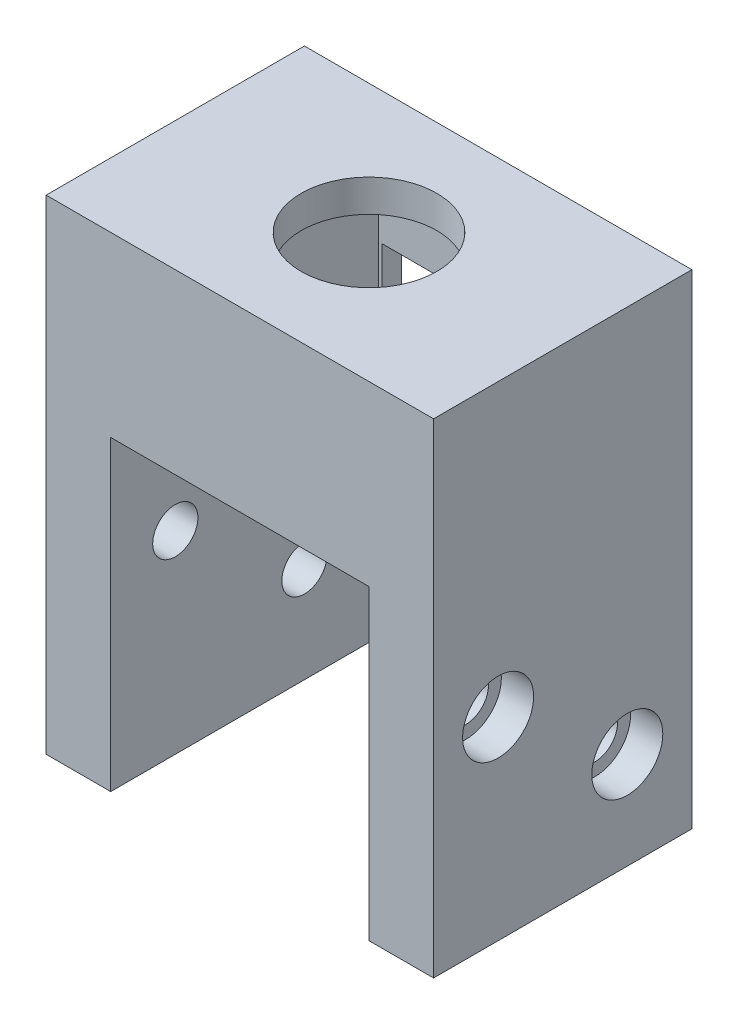
SolidWorks part; units mm, degrees
ref_plane "前视基准面" through (0, 0, 0) normal (0, 0, 1) x (1, 0, 0)
ref_plane "上视基准面" through (0, 0, 0) normal (0, 1, 0) x (1, 0, 0)
ref_plane "右视基准面" through (0, 0, 0) normal (1, 0, 0) x (0, 0, -1)
other "Configuration Table"
sketch "草图1" plane through (0, 0, 0) normal (0, 1, 0) x (1, 0, 0)
  line L0 (-4, 0) -> (4, 0) construction
  line L1 (-4, -4) -> (4, -4)
  line L2 (-4, -4) -> (-4, 4)
  line L3 (-4, 4) -> (4, 4)
  line L4 (4, -4) -> (4, 4)
  line L10 (-4, 4) -> (-6, 4)
  line L11 (-4, 4) -> (-4, -4)
  line L12 (-4, -4) -> (-6, -4)
  line L13 (-6, 4) -> (-6, -4)
  line L14 (4, 4) -> (6, 4)
  line L15 (4, 4) -> (4, -4)
  line L16 (4, -4) -> (6, -4)
  line L17 (6, 4) -> (6, -4)
  circle A0 centre (0, 0) radius 2.1
  dimension "D3" = 4.2
  dimension "D5" = 2
  dimension "D1" = 8
  dimension "D2" = 4
  dimension "D4" = 8
extrude "凸台-拉伸1" add sketch "草图1" along normal blind 1 contours L2 L3 L4 L1 | A0
extrude "凸台-拉伸2" add sketch "草图1<6>" against normal blind 15 from surface separate body contours L10 L13 L12 L2 L11 | L17 L14 L15 L4 L16 region at (-5, 0, 0) region at (5, 0, 0) starting at face at (0, 1, 0)
sketch "草图1<6>" plane through (0, 0, 0) normal (0, 1, 0) x (1, 0, 0) same geometry as "草图1"
sketch "草图2" plane through (0, 0, 0) normal (0, -1, 0) x (1, 0, 0)
  line L0 (4, -4) -> (4, 4) construction
  line L1 (4, 3.4) -> (-4, 3.4)
  line L2 (4, 3.4) -> (4, 4)
  line L3 (4, 4) -> (-4, 4)
  line L4 (-4, 3.4) -> (-4, 4)
  line L5 (-4, 4) -> (4, 4) construction
  line L6 (-4, -4) -> (-4, 4) construction
  line L7 (4, -3.4) -> (-4, -3.4)
  line L8 (4, -3.4) -> (4, -4)
  line L9 (4, -4) -> (-4, -4)
  line L10 (-4, -3.4) -> (-4, -4)
  line L12 (-4, 4) -> (-3.1, 4)
  line L13 (-4, 4) -> (-4, -4)
  line L14 (-4, -4) -> (-3.1, -4)
  line L15 (-3.1, 4) -> (-3.1, -4)
  line L16 (4, 4) -> (3.1, 4)
  line L17 (4, 4) -> (4, -4)
  line L18 (4, -4) -> (3.1, -4)
  line L19 (3.1, 4) -> (3.1, -4)
  line M14 (4, 4) -> (-4, 4)
  line M15 (-4, 4) -> (-4, -4)
  line M16 (-4, -4) -> (4, -4)
  line M17 (4, -4) -> (4, 4)
  dimension "D1" = 0.6
  dimension "D2" = 0.9
extrude "凸台-拉伸3" add sketch "草图2" along normal blind 4.5 contours L15 L3 L1 M15 | L19 L3 L15 L1 | L19 L1 M14 M17 | L1 L19 L7 M17 | L7 L19 M16 M17 | L19 L7 L15 L9 | L15 L7 M15 M16 | L15 L1 L7 M15 region at (3.55, 0, 0) region at (3.55, 0, 3.7) region at (0, 0, 3.7) region at (3.55, 0, -3.7) region at (-3.55, 0, 0) region at (-3.55, 0, 3.7) region at (0, 0, -3.7) region at (-3.55, 0, -3.7)
sketch "草图3" plane through (0, 0, -4) normal (0, 0, -1) x (-1, 0, 0)
  line L0 (4, -4.5) -> (-4, -4.5) construction
  line L1 (-3, -4.5) -> (-1.4, -4.5)
  line L2 (-3, -4.5) -> (-3, -2.5)
  line L3 (-3, -2.5) -> (-1.4, -2.5)
  line L4 (-1.4, -4.5) -> (-1.4, -2.5)
  line L5 (-4, -14) -> (-4, -4.5) construction
  line L6 (1.4, -4.5) -> (3, -4.5)
  line L7 (1.4, -4.5) -> (1.4, -2.5)
  line L8 (1.4, -2.5) -> (3, -2.5)
  line L9 (3, -4.5) -> (3, -2.5)
  line L10 (4, -14) -> (4, -4.5) construction
  line M13 (-4, -4.5) -> (4, -4.5)
  dimension "D1" = 2
  dimension "D2" = 1
  dimension "D3" = 1
  dimension "D4" = 1.6
extrude "切除-拉伸1" cut sketch "草图3" against normal up to next contours L4 L3 L2 M13 | L9 L8 L7 M13 region at (2.2, -3.5, -4) region at (-2.2, -3.5, -4)
sketch "草图4" plane through (6, 0, 0) normal (1, 0, 0) x (0, 0, -1)
  line L0 (-4, -14) -> (4, -14) construction
  line L1 (-4, -14) -> (-4, 1) construction
  line L2 (4, -14) -> (4, 1) construction
  circle A0 centre (-2, -8) radius 1.1
  circle A1 centre (-2, -8) radius 0.7
  circle A2 centre (2, -11) radius 1.1
  circle A3 centre (2, -11) radius 0.7
  dimension "D1" = 1.4
  dimension "D2" = 2.2
  dimension "D3" = 6
  dimension "D4" = 3
  dimension "D5" = 2
  dimension "D6" = 2
extrude "切除-拉伸2" cut sketch "草图4" against normal through all contours A1 | A3
extrude "切除-拉伸3" cut sketch "草图4<3>" against normal blind 1 contours A0 | A2
sketch "草图4<3>" plane through (6, 0, 0) normal (1, 0, 0) x (0, 0, -1) same geometry as "草图4"
extrude "切除-拉伸4" cut sketch "草图4<4>" along normal blind 1 from surface contours A0 | A2 starting at face at (-6, -8, 1.3)
sketch "草图4<4>" plane through (6, 0, 0) normal (1, 0, 0) x (0, 0, -1) same geometry as "草图4"
